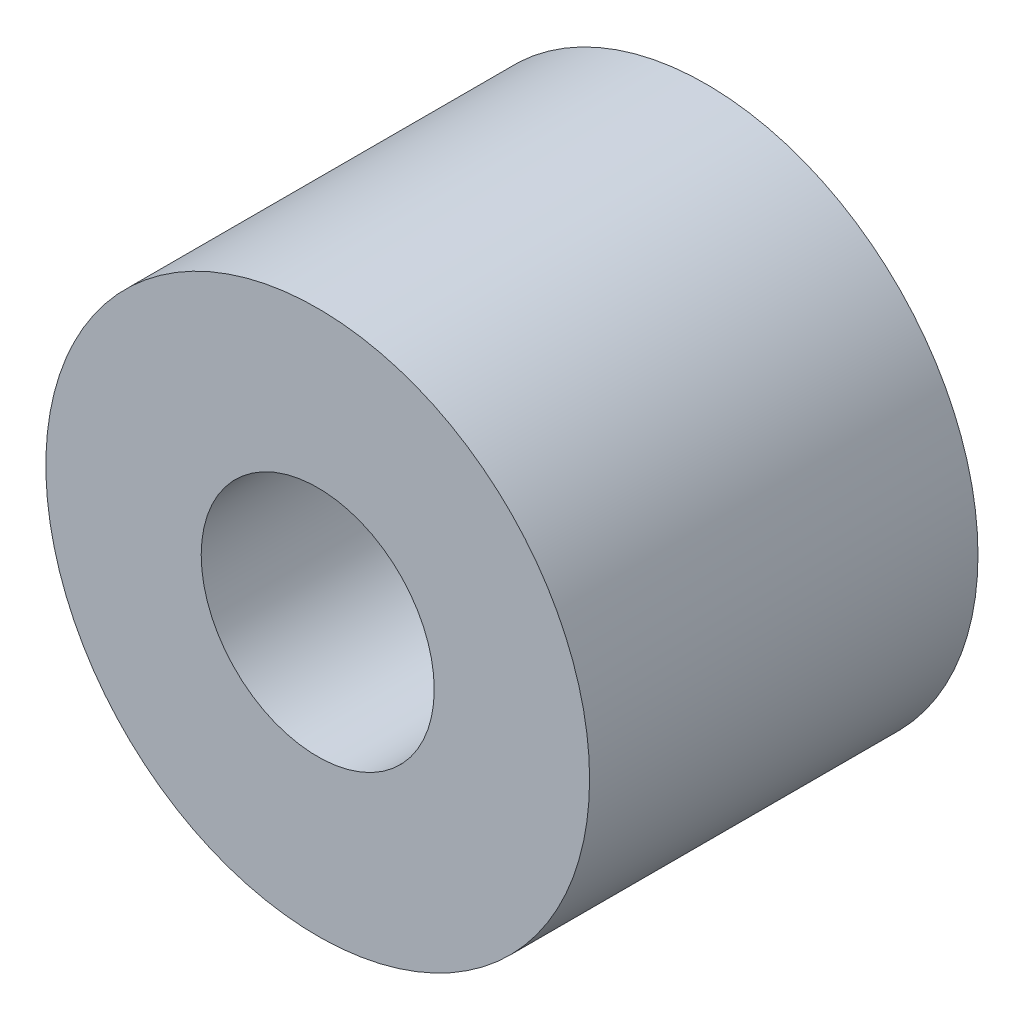
SolidWorks part; units mm, degrees
ref_plane "Alzado" through (0, 0, 0) normal (0, 0, 1) x (1, 0, 0)
ref_plane "Planta" through (0, 0, 0) normal (0, 1, 0) x (1, 0, 0)
ref_plane "Vista lateral" through (0, 0, 0) normal (1, 0, 0) x (0, 0, -1)
sketch "General" plane through (0, 0, 0) normal (0, 0, 1) x (1, 0, 0)
  line L0 (0, 0) -> (0, 6925.6593) construction
  line L1 (0, 0) -> (6925.6593, 0) construction
  line L2 (-72.5848, 38.7243) -> (-55.2109, 28.8174) construction
  line L3 (-55.2109, 28.8174) -> (-20, 0) construction
  line L4 (-20, 0) -> (-74.4401, -11.2413) construction
  line L5 (-74.4401, -11.2413) -> (-72.5848, 38.7243) construction
  line L6 (-30.4437, 72.2523) -> (-55.2109, 28.8174) construction
  line L7 (-72.5848, 38.7243) -> (-30.4437, 72.2523) construction
  line L8 (-74.4401, -11.2413) -> (-35.25, -19.25) construction
  line L9 (65.1803, -5) -> (-49934.8197, -5) construction
  line L10 (0, 20) -> (0, 30) construction
  line L11 (-46.5, -33.5) -> (0, -33.5) construction
  line L12 (-46.5, -33.5) -> (-46.5, -5) construction
  line L13 (-46.5, -5) -> (0, -5) construction
  line L14 (0, -33.5) -> (0, -5) construction
  line L15 (-46.5, -33.5) -> (0, -5) construction
  line L16 (-46.5, -5) -> (0, -33.5) construction
  line L17 (-20, 20) -> (-20, 30) construction
  line L18 (20, 20) -> (20, 30) construction
  line L19 (0, 45) -> (0, 35) construction
  line L20 (35, 45) -> (35, 35) construction
  line L21 (-35, 45) -> (-35, 35) construction
  line L22 (-30.4437, 72.2523) -> (-33.0838, 81.8975)
  line L23 (-58.27, 20.9833) -> (-27.0745, -4.5478)
  line L24 (-42.6722, 8.2178) -> (-37.6054, 14.4087) construction
  line L25 (-58.27, 20.9833) -> (-59.2833, 19.7451)
  line L26 (-59.2833, 19.7451) -> (-28.0879, -5.7859)
  line L27 (-28.0879, -5.7859) -> (-27.0745, -4.5478)
  line L28 (-38.3494, 82.9421) -> (-72.5848, 38.7243)
  circle A0 centre (-20, 0) radius 1.5
  circle A1 centre (-55.2109, 28.8174) radius 1.5
  circle A2 centre (-72.5848, 38.7243) radius 1.5 construction
  circle A3 centre (-74.4401, -11.2413) radius 1.5
  circle A4 centre (-30.4437, 72.2523) radius 1.5 construction
  arc A5 (-30.4437, 72.2523) -> (-55.2109, 28.8174) centre (23.188, 12.892) ccw
  arc A6 (-55.2109, 28.8174) -> (-20, 0) centre (10.9706, 73.7619) ccw
  circle A7 centre (-35.25, -19.25) radius 10 construction
  arc A8 (-20, 20) -> (20, 20) centre (0, 20) ccw construction
  arc A9 (20, 30) -> (-20, 30) centre (0, 30) ccw construction
  arc A10 (-20, 0) -> (0, -2.5403) centre (0, 77.4597) ccw
  arc A11 (35, 45) -> (-35, 45) centre (0, 45) ccw construction
  arc A12 (-35, 35) -> (35, 35) centre (0, 35) ccw construction
  circle A13 centre (-55.2109, 28.8174) radius 3.5
  circle A14 centre (-20, 0) radius 3.5
  circle A15 centre (-72.5848, 38.7243) radius 3.5
  circle A16 centre (-74.4401, -11.2413) radius 3.5
  arc A17 (-33.0838, 81.8975) -> (-38.3494, 82.9421) centre (-35.9773, 81.1055) ccw
  point P19 (-23.25, -19.25)
  point P26 (0, 25)
  point P35 (0, 40)
  point P48 (0, 0)
  dimension "D1" = 40
  dimension "D2" = 3
  dimension "D3" = 45.5
  dimension "D4" = 50
  dimension "D7" = 80
  dimension "D8" = 80
  dimension "D10" = 35.25
  dimension "D17" = 20
  dimension "D18" = 80
  dimension "D20" = 35
  dimension "D21" = 20
  dimension "D24" = 7
  dimension "D25" = 1.6
  dimension "D27" = 3
  dimension "D5" = 20
  dimension "D6" = 90
  dimension "D9" = 50
  dimension "D11" = 14.25
  dimension "D12" = 40
  dimension "D13" = 5
  dimension "D14" = 46.5
  dimension "D15" = 28.5
  dimension "D16" = 10
  dimension "D19" = 10
  dimension "D22" = 135
  dimension "D23" = 10
  dimension "D26" = 8
sketch "Croquis2" plane through (0, 0, 0) normal (0, 0, 1) x (1, 0, 0)
  line L0 (-55.2109, 28.8174) -> (-57.4276, 26.1089)
  line L4 (-55.2109, 28.8174) -> (-62.8111, 19.531) construction
  line L5 (-62.8111, 19.531) -> (-27.6002, -9.2864) construction
  line L6 (-27.6002, -9.2864) -> (-20, 0) construction
  line L7 (-55.2109, 28.8174) -> (-20, 0) construction
  line L8 (-57.4276, 26.1089) -> (-59.0134, 16.4229)
  line L9 (-59.0134, 16.4229) -> (-31.3979, -6.1782)
  line L10 (-31.3979, -6.1782) -> (-22.2167, -2.7085)
  line L11 (-42.6722, 8.2178) -> (-37.6054, 14.4087) construction
  circle A1 centre (-55.2109, 28.8174) radius 1.5
  arc A2 (-53.1817, 25.9657) -> (-57.4276, 26.1089) centre (-55.2109, 28.8174) ccw
  circle A3 centre (-55.2109, 28.8174) radius 3.5 construction
  arc A10 (-55.2109, 28.8174) -> (-20, 0) centre (10.9706, 73.7619) ccw construction
  arc A11 (-53.1817, 25.9657) -> (-23.1967, 1.4252) centre (10.9706, 73.7619) ccw
  circle A12 centre (-20, 0) radius 3.5 construction
  arc A13 (-23.1967, 1.4252) -> (-22.2167, -2.7085) centre (-20, 0) cw
  circle A14 centre (-20, 0) radius 1.5
  circle A15 centre (-20, 0) radius 1.5 construction
  point P28 (-45.2056, 5.1223)
  dimension "D1" = 60
  dimension "D2" = 12
extrude "Saliente-Extruir1" add sketch "Croquis2" along normal blind 40 rebuild error yes
ref_plane "Plano1" through (-31.625, 42.1037, 0) normal (0.6006, -0.7996, 0) x (-0.7996, -0.6006, 0)
sketch "Croquis14" plane through (-31.625, 42.1037, 0) normal (0.6006, -0.7996, 0) x (-0.7996, -0.6006, 0)
  line L0 (27.0867, 0) -> (27.0867, -30)
  line L1 (27.0867, -40) -> (27.0867, 0) construction
  line L2 (27.0867, -30) -> (37.8246, -40)
  line L3 (30.4059, -40) -> (37.4645, -40) construction
  line L4 (37.8246, -40) -> (-53.0712, -40)
  line L5 (-53.0712, -40) -> (-53.0712, 0)
  line L6 (-159963.0739, 0) -> (199843.3373, 0) construction
  line L7 (-53.0712, 0) -> (27.0867, 0)
revolve "Cortar-Revolución1" cut sketch "Croquis14" angle 360 about L5 rebuild error yes
sketch "Croquis8" plane through (0, 0, 0) normal (0, 0, 1) x (1, 0, 0)
  circle A0 centre (-55.2109, 28.8174) radius 1.5
  circle A1 centre (-55.2109, 28.8174) radius 3.5
  arc A3 (-53.1817, 25.9657) -> (-57.4276, 26.1089) centre (-55.2109, 28.8174) ccw construction
  circle A4 centre (-55.2109, 28.8174) radius 1.5 construction
extrude "Eje superior" add sketch "Croquis8" along normal blind 5
sketch "Croquis10" plane through (0, 0, 5) normal (0, 0, 1) x (1, 0, 0)
  circle A0 centre (-55.2109, 28.8174) radius 4
  dimension "D1" = 8
extrude "Cortar-Extruir1" cut sketch "Croquis10" along normal through all rebuild error yes
sketch "Croquis12" plane through (0, 0, 0) normal (0, 0, -1) x (-1, 0, 0)
  circle A0 centre (20, 0) radius 0.0872 construction
  circle A1 centre (20, 0) radius 3.5
  circle A3 centre (20, 0) radius 3.5 construction
  circle A4 centre (20, 0) radius 1.5
  circle A5 centre (20, 0) radius 1.5 construction
extrude "Saliente-Extruir3" add sketch "Croquis12" against normal up to vertex rebuild error yes up to point (-22.2062, -2.7171, 33.1304)
sketch "Croquis13" plane through (-63.0129, 19.4664, 0) normal (0.6303, 0.7763, 0) x (0, 0, 1)
  line L0 (12, -34.3363) -> (12, 48962.3524) construction
  circle A0 centre (12, 91.1889) radius 2
  circle A1 centre (12, 51.1889) radius 2
  circle A2 centre (12, 71.1889) radius 2
  dimension "D1" = 12
  dimension "D2" = 4
  dimension "D3" = 20
  dimension "D4" = 20
  dimension "D5" = 10
extrude "Cortar-Extruir4" [suppressed] cut sketch "Croquis13" against normal blind 7
sketch "Croquis15" plane through (0, 0, 0) normal (0, 0, -1) x (-1, 0, 0)
  circle A0 centre (20, 0) radius 4.5
  circle A1 centre (20, 0) radius 3.5 construction
  dimension "D1" = 1
extrude "Cortar-Extruir5" cut sketch "Croquis15" against normal blind 5.5 rebuild error yes
mirror "Simetría1" rebuild error yes
